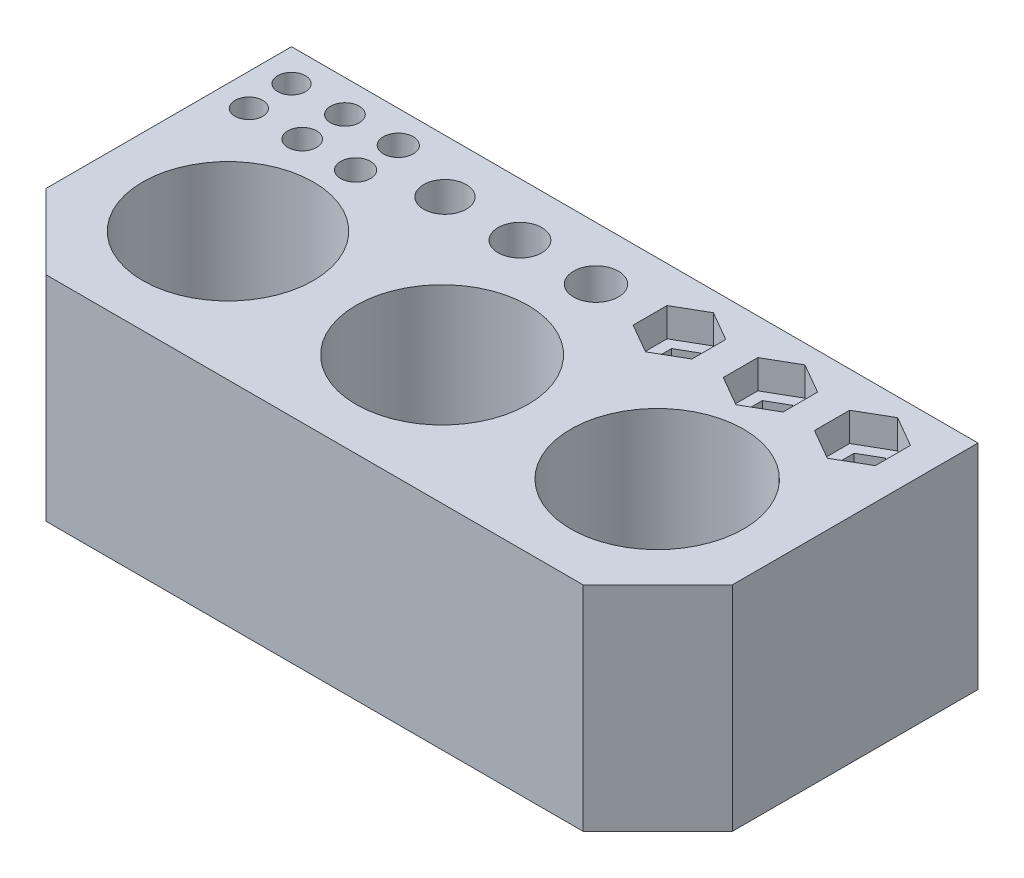
SolidWorks part; units mm, degrees
ref_plane "Front Plane" through (0, 0, 0) normal (0, 0, 1) x (1, 0, 0)
ref_plane "Top Plane" through (0, 0, 0) normal (0, 1, 0) x (1, 0, 0)
ref_plane "Right Plane" through (0, 0, 0) normal (1, 0, 0) x (0, 0, -1)
sketch "Sketch1" plane through (0, 0, 0) normal (0, 1, 0) x (1, 0, 0)
  line L0 (7.95, -2.95) -> (11.95, -2.95) construction
  line L1 (-32.15, 15) -> (32.15, 15)
  line L2 (-32.15, 15) -> (-32.15, -15)
  line L3 (-32.15, -15) -> (32.15, -15)
  line L4 (32.15, 15) -> (32.15, -15)
  line L5 (-32.15, 15) -> (32.15, -15) construction
  line L6 (-32.15, -15) -> (32.15, 15) construction
  line L7 (9.1857, 6.8246) -> (11.9357, 8.4123)
  line L8 (11.9357, 8.4123) -> (11.9357, 11.5877)
  line L9 (11.9357, 11.5877) -> (9.1857, 13.1754)
  line L10 (9.1857, 13.1754) -> (6.4357, 11.5877)
  line L11 (6.4357, 11.5877) -> (6.4357, 8.4123)
  line L12 (6.4357, 8.4123) -> (9.1857, 6.8246)
  line L13 (17.7071, 6.7668) -> (20.5071, 8.3834)
  line L14 (20.5071, 8.3834) -> (20.5071, 11.6166)
  line L15 (20.5071, 11.6166) -> (17.7071, 13.2332)
  line L16 (17.7071, 13.2332) -> (14.9071, 11.6166)
  line L17 (14.9071, 11.6166) -> (14.9071, 8.3834)
  line L18 (14.9071, 8.3834) -> (17.7071, 6.7668)
  line L19 (28.15, -2.95) -> (32.15, -2.95) construction
  line L20 (-0.1, -11) -> (-0.1, -15) construction
  line L21 (-8.15, -2.95) -> (-12.15, -2.95) construction
  line L22 (-28.15, -2.95) -> (-32.15, -2.95) construction
  line L23 (-17.75, 8) -> (-17.75, 12) construction
  line L24 (3.4643, 10) -> (1.3643, 10) construction
  line L25 (3.4643, 10) -> (6.4357, 10) construction
  line L26 (-29.15, 12) -> (-19.15, 12) construction
  line L27 (-29.15, 8) -> (-19.15, 8) construction
  line L28 (-29.15, 12) -> (-29.15, 8) construction
  line L29 (-24.15, 12) -> (-24.15, 8) construction
  line L30 (-19.15, 12) -> (-19.15, 8) construction
  line L31 (9.1857, 10) -> (9.1857, 13.1754) construction
  line L32 (26.3286, 6.7091) -> (29.1786, 8.3546)
  line L33 (29.1786, 8.3546) -> (29.1786, 11.6454)
  line L34 (29.1786, 11.6454) -> (26.3286, 13.2909)
  line L35 (26.3286, 13.2909) -> (23.4786, 11.6454)
  line L36 (23.4786, 11.6454) -> (23.4786, 8.3546)
  line L37 (23.4786, 8.3546) -> (26.3286, 6.7091)
  line L38 (11.9357, 10) -> (14.9071, 10) construction
  line L39 (20.5071, 10) -> (23.4786, 10) construction
  line L40 (29.1786, 10) -> (32.15, 10) construction
  line L41 (-17.75, 10) -> (-14.7786, 10) construction
  line L42 (-10.7786, 10) -> (-7.8071, 10) construction
  line L43 (-3.7071, 10) -> (-0.7357, 10) construction
  line L44 (17.7071, 10) -> (17.7071, 13.2332) construction
  line L45 (26.3286, 10) -> (26.3286, 13.2909) construction
  circle A0 centre (9.1857, 10) radius 2.75 construction
  circle A2 centre (-12.7786, 10) radius 2
  circle A3 centre (-24.15, 12) radius 1.35
  circle A4 centre (-0.1, -2.95) radius 8.05
  circle A5 centre (-5.7571, 10) radius 2.05
  circle A6 centre (20.05, -2.95) radius 8.1
  circle A7 centre (-19.15, 12) radius 1.4
  circle A8 centre (1.3643, 10) radius 2.1
  circle A9 centre (-29.15, 12) radius 1.3
  circle A10 centre (17.7071, 10) radius 2.8 construction
  circle A11 centre (-24.15, 8) radius 1.35
  circle A12 centre (-29.15, 8) radius 1.3
  circle A13 centre (-19.15, 8) radius 1.4
  circle A14 centre (-20.15, -2.95) radius 8
  circle A15 centre (26.3286, 10) radius 2.85 construction
  point P0 (0, 0)
  dimension "D1" = 5.5
  dimension "D2" = 16.1
  dimension "D3" = 4
  dimension "D4" = 2.7
  dimension "D7" = 4.1
  dimension "D8" = 16.2
  dimension "D9" = 2.8
  dimension "D10" = 4.2
  dimension "D11" = 2.6
  dimension "D12" = 5.6
  dimension "D16" = 16
  dimension "D5" = 4
  dimension "D17" = 3
  dimension "D19" = 5
  dimension "D20" = 5
  dimension "D21" = 3
  dimension "D23" = 5.7
  dimension "D6" = 30
  dimension "D13" = 4
extrude "Boss-Extrude1" add sketch "Sketch1" along normal blind 20 contours L2 L3 L4 L1
extrude "Varillas huecas" cut sketch "Sketch1<3>" against normal blind 15 from surface contours A4 | A6 | A14 starting at face at (0, 20, 0)
sketch "Sketch1<3>" plane through (0, 0, 0) normal (0, 1, 0) x (1, 0, 0) same geometry as "Sketch1"
extrude "Tornillos Alem" cut sketch "Sketch1<4>" against normal blind 12 from surface contours A7 | A3 | A9 starting at face at (-20.15, 20, -5.05)
sketch "Sketch1<4>" plane through (0, 0, 0) normal (0, 1, 0) x (1, 0, 0) same geometry as "Sketch1"
extrude "Tornillos PCB" cut sketch "Sketch1<6>" against normal blind 2.7 from surface contours L10 L11 L12 L7 L8 L9 | L18 L13 L14 L15 L16 L17 | L37 L32 L33 L34 L35 L36 starting at face at (-19.15, 20, -13.4)
sketch "Sketch1<6>" plane through (0, 0, 0) normal (0, 1, 0) x (1, 0, 0) same geometry as "Sketch1"
extrude "Varillas servos" cut sketch "Sketch1<5>" against normal blind 20 from surface contours A8 | A5 | A2 starting at face at (9.1857, 20, -10)
sketch "Sketch1<5>" plane through (0, 0, 0) normal (0, 1, 0) x (1, 0, 0) same geometry as "Sketch1"
chamfer "Chamfer1" distance 7 angle 45 2 edges at (32.15, 10, 15) (-32.15, 10, 15)
sketch "Sketch2" plane through (0, 17.3, 0) normal (0, 1, 0) x (1, 0, 0)
  line L0 (23.4786, 11.6454) -> (23.4786, 8.3546) construction
  line L1 (23.4786, 8.3546) -> (26.3286, 6.7091) construction
  line L2 (26.3286, 6.7091) -> (29.1786, 8.3546) construction
  line L3 (29.1786, 8.3546) -> (29.1786, 11.6454) construction
  line L4 (29.1786, 11.6454) -> (26.3286, 13.2909) construction
  line L5 (26.3286, 13.2909) -> (23.4786, 11.6454) construction
  line L6 (14.9071, 11.6166) -> (14.9071, 8.3834) construction
  line L7 (14.9071, 8.3834) -> (17.7071, 6.7668) construction
  line L8 (17.7071, 6.7668) -> (20.5071, 8.3834) construction
  line L9 (20.5071, 8.3834) -> (20.5071, 11.6166) construction
  line L10 (20.5071, 11.6166) -> (17.7071, 13.2332) construction
  line L11 (17.7071, 13.2332) -> (14.9071, 11.6166) construction
  line L12 (11.9357, 11.5877) -> (9.1857, 13.1754) construction
  line L13 (9.1857, 13.1754) -> (6.4357, 11.5877) construction
  line L14 (6.4357, 11.5877) -> (6.4357, 8.4123) construction
  line L15 (6.4357, 8.4123) -> (9.1857, 6.8246) construction
  line L16 (9.1857, 6.8246) -> (11.9357, 8.4123) construction
  line L17 (11.9357, 8.4123) -> (11.9357, 11.5877) construction
  line L18 (23.4786, 11.6454) -> (23.4786, 8.3546) construction
  line L19 (23.4786, 8.3546) -> (26.3286, 6.7091) construction
  line L20 (26.3286, 6.7091) -> (29.1786, 8.3546) construction
  line L21 (29.1786, 8.3546) -> (29.1786, 11.6454) construction
  line L22 (29.1786, 11.6454) -> (26.3286, 13.2909) construction
  line L23 (26.3286, 13.2909) -> (23.4786, 11.6454) construction
  line L24 (14.9071, 11.6166) -> (14.9071, 8.3834) construction
  line L25 (14.9071, 8.3834) -> (17.7071, 6.7668) construction
  line L26 (17.7071, 6.7668) -> (20.5071, 8.3834) construction
  line L27 (20.5071, 8.3834) -> (20.5071, 11.6166) construction
  line L28 (20.5071, 11.6166) -> (17.7071, 13.2332) construction
  line L29 (17.7071, 13.2332) -> (14.9071, 11.6166) construction
  line L30 (11.9357, 11.5877) -> (9.1857, 13.1754) construction
  line L31 (9.1857, 13.1754) -> (6.4357, 11.5877) construction
  line L32 (6.4357, 11.5877) -> (6.4357, 8.4123) construction
  line L33 (6.4357, 8.4123) -> (9.1857, 6.8246) construction
  line L34 (9.1857, 6.8246) -> (11.9357, 8.4123) construction
  line L35 (11.9357, 8.4123) -> (11.9357, 11.5877) construction
  line L36 (24.4786, 11.0681) -> (24.4786, 8.9319)
  line L37 (24.4786, 8.9319) -> (26.3286, 7.8638)
  line L38 (26.3286, 7.8638) -> (28.1786, 8.9319)
  line L39 (28.1786, 8.9319) -> (28.1786, 11.0681)
  line L40 (28.1786, 11.0681) -> (26.3286, 12.1362)
  line L41 (26.3286, 12.1362) -> (24.4786, 11.0681)
  line L42 (15.9071, 11.0392) -> (15.9071, 8.9608)
  line L43 (15.9071, 8.9608) -> (17.7071, 7.9215)
  line L44 (17.7071, 7.9215) -> (19.5071, 8.9608)
  line L45 (19.5071, 8.9608) -> (19.5071, 11.0392)
  line L46 (19.5071, 11.0392) -> (17.7071, 12.0785)
  line L47 (17.7071, 12.0785) -> (15.9071, 11.0392)
  line L48 (10.9357, 11.0104) -> (9.1857, 12.0207)
  line L49 (9.1857, 12.0207) -> (7.4357, 11.0104)
  line L50 (7.4357, 11.0104) -> (7.4357, 8.9896)
  line L51 (7.4357, 8.9896) -> (9.1857, 7.9793)
  line L52 (9.1857, 7.9793) -> (10.9357, 8.9896)
  line L53 (10.9357, 8.9896) -> (10.9357, 11.0104)
  dimension "D1" = 1
extrude "Cut-Extrude5" cut sketch "Sketch2" against normal up to next
extrude "Cut-Extrude6" cut sketch "Sketch1<7>" against normal blind 3.5 from surface contours A13 | A11 | A12 starting at face at (1.3643, 20, -12.1)
sketch "Sketch1<7>" plane through (0, 0, 0) normal (0, 1, 0) x (1, 0, 0) same geometry as "Sketch1"
